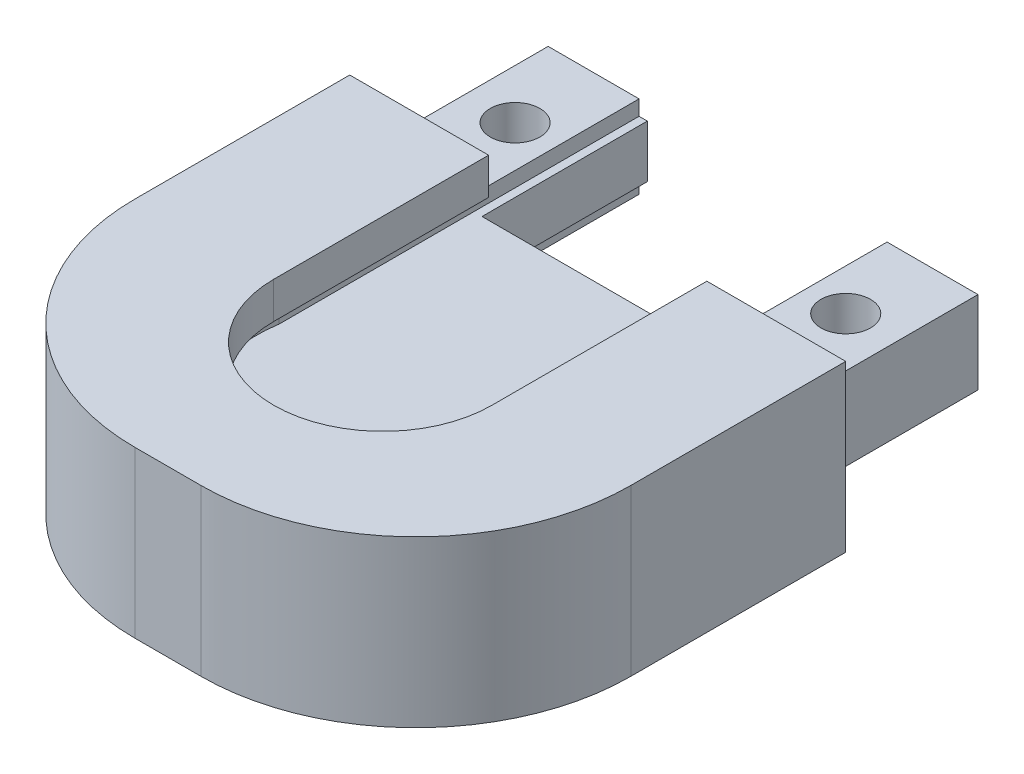
SolidWorks part; units mm, degrees
ref_plane "Front Plane" through (0, 0, 0) normal (0, 0, 1) x (1, 0, 0)
ref_plane "Top Plane" through (0, 0, 0) normal (0, 1, 0) x (1, 0, 0)
ref_plane "Right Plane" through (0, 0, 0) normal (1, 0, 0) x (0, 0, -1)
sketch "Sketch1" plane through (0, 0, 0) normal (0, 1, 0) x (1, 0, 0)
  line L0 (0, 0) -> (6, 0)
  line L1 (6, 0) -> (6, -10)
  line L2 (6, -10) -> (20, -10)
  line L3 (20, -10) -> (20, 0)
  line L4 (20, 0) -> (26, 0)
  line L5 (26, 0) -> (26, -10)
  line L7 (0, -10) -> (0, 0)
  line L8 (0, -10) -> (-2, -10)
  line L9 (-2, -10) -> (-2, -36)
  line L10 (-2, -36) -> (28, -36)
  line L11 (28, -36) -> (28, -10)
  line L12 (28, -10) -> (26, -10)
  line L13 (3, 0) -> (3, -5) construction
  line L14 (13, -10) -> (13, 0) construction
  circle A0 centre (3, -5) radius 1.5
  circle A1 centre (23, -5) radius 1.5
  point P18 (0, 0)
  dimension "D9" = 3
  dimension "D1" = 36
  dimension "D2" = 30
  dimension "D3" = 10
  dimension "D4" = 6
  dimension "D5" = 2
  dimension "D6" = 6
  dimension "D7" = 2
  dimension "D8" = 5
extrude "Boss-Extrude1" add sketch "Sketch1" along normal blind 5
sketch "Sketch2" plane through (0, 0, 36) normal (0, 0, 1) x (1, 0, 0)
  line L0 (-2, 5) -> (-2, 7.5)
  line L1 (-2, 7.5) -> (28, 7.5)
  line L2 (28, 7.5) -> (28, 5)
  line L3 (28, 5) -> (-2, 5)
  line L4 (-2, 0) -> (28, 0)
  line L5 (28, 0) -> (28, -2.5)
  line L6 (28, -2.5) -> (-2, -2.5)
  line L7 (-2, -2.5) -> (-2, 0)
  point P12 (27.9848, 5)
  dimension "D1" = 10
extrude "Boss-Extrude2" add sketch "Sketch2" against normal up to surface (26 mm away) up to face at (13, 2.5, 10)
fillet "Fillet1" radius 13 2 edges at (28, 2.5, 36) (-2, 2.5, 36)
ref_plane "Plane1" through (0, 2.5, 0) normal (0, -1, 0) x (-1, 0, 0)
sketch "Sketch3" plane through (0, 0, 10) normal (0, 0, -1) x (-1, 0, 0)
  line L0 (-19.6, 7.5) -> (-19.6, 5.2875)
  line L1 (2, 7.5) -> (-28, 7.5) construction
  line L2 (-19.6, 5.2875) -> (-20.5, 5.2875)
  line L3 (-20.5, 5.2875) -> (-20.5, 4.0875)
  line L4 (-20.5, 4.0875) -> (-13, 4.0875)
  line L5 (-13, 4.0875) -> (-5.5, 4.0875)
  line L6 (-5.5, 4.0875) -> (-5.5, 5.2875)
  line L7 (-5.5, 5.2875) -> (-6.4, 5.2875)
  line L8 (-6.4, 5.2875) -> (-6.4, 7.5)
  line L9 (-6.4, 7.5) -> (-19.6, 7.5)
  line L10 (-20, 2.5) -> (-6, 2.5) construction
  line L11 (-20, 5) -> (-20, 0) construction
  line L12 (-6, 5) -> (-6, 0) construction
  line L13 (-13, 2.5) -> (-13, 4.0875) construction
  point P18 (-10.7323, 2.1125)
  point P19 (-19.8114, 2.1125)
  dimension "D1" = 1.2
  dimension "D2" = 3.4125
  dimension "D3" = 13.2
  dimension "D4" = 15
extrude "Cut-Extrude1" cut sketch "Sketch3" against normal blind 13 and the other way through all
sketch "Sketch4" plane through (0, 4.0875, 0) normal (0, 1, 0) x (1, 0, 0)
  line L0 (6.4, -23) -> (19.6, -23) construction
  circle A0 centre (13, -23) radius 7.6
  dimension "D1" = 15.2
extrude "Cut-Extrude2" cut sketch "Sketch4" along normal up to surface (1.2 mm away) up to face at (5.95, 5.2875, 16.5)
sketch "Sketch5" plane through (0, 4.0875, 0) normal (0, 1, 0) x (1, 0, 0)
  line L0 (6.4, -23) -> (19.6, -23) construction
  circle A0 centre (13, -23) radius 6.6
  dimension "D1" = 13.2
extrude "Cut-Extrude3" cut sketch "Sketch5" along normal through all
mirror "Mirror1" about plane through (0, 2.5, 0) normal (0, -1, 0) of "Cut-Extrude1"
sketch "Sketch6" plane through (0, 0.9125, 0) normal (0, -1, 0) x (1, 0, 0)
  line L0 (6.4, 23) -> (19.6, 23) construction
  circle A0 centre (13, 23) radius 7.6
  dimension "D1" = 15.2
extrude "Cut-Extrude4" cut sketch "Sketch6" along normal up to surface (1.2 mm away) up to face at (5.95, -0.2875, 16.5)
sketch "Sketch7" plane through (0, 0.9125, 0) normal (0, -1, 0) x (1, 0, 0)
  line L0 (6.4, 23) -> (19.6, 23) construction
  circle A0 centre (13, 23) radius 6.6
  dimension "D1" = 13.2
extrude "Cut-Extrude5" cut sketch "Sketch7" along normal through all
